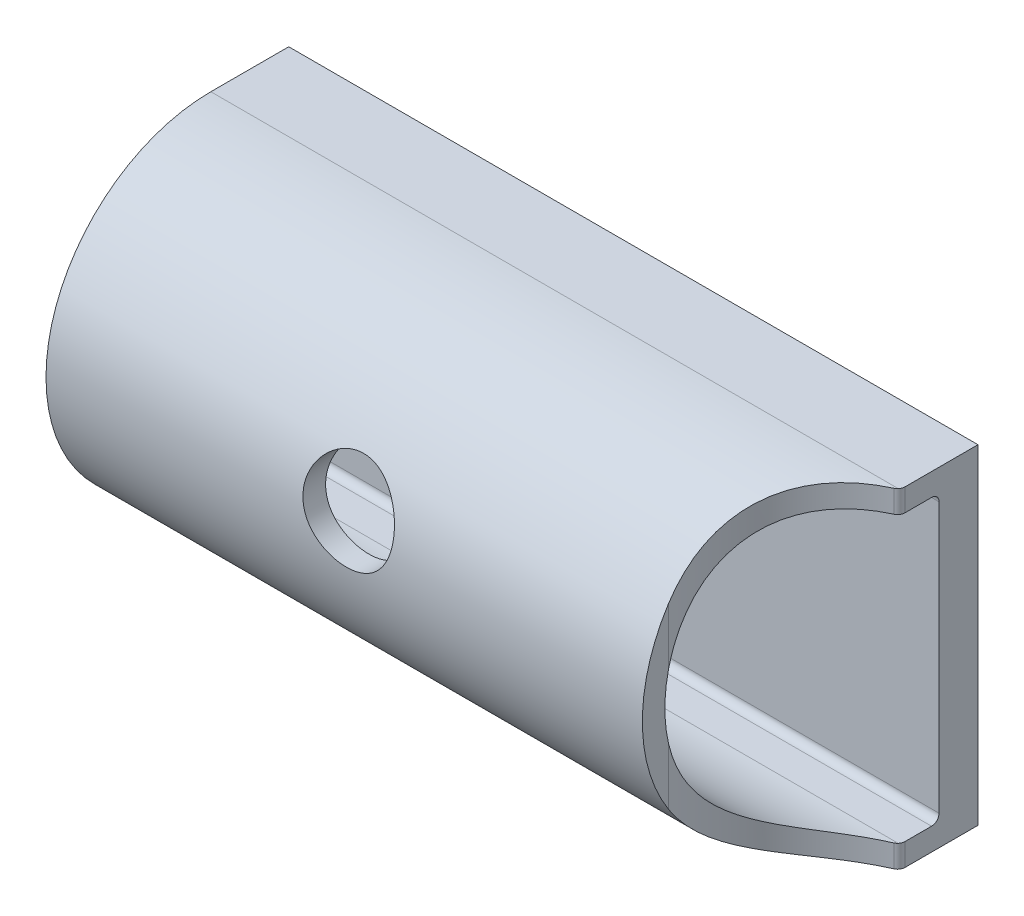
SolidWorks part; units mm, degrees
ref_plane "Front Plane" through (0, 0, 0) normal (0, 0, 1) x (1, 0, 0)
ref_plane "Top Plane" through (0, 0, 0) normal (0, 1, 0) x (1, 0, 0)
ref_plane "Right Plane" through (0, 0, 0) normal (1, 0, 0) x (0, 0, -1)
sketch "Sketch1" plane through (0, 0, 0) normal (0, 0, 1) x (1, 0, 0)
  line L0 (22, 2) -> (-2, 2) construction
  line L1 (-22, -9) -> (22, -9)
  line L2 (-22, -9) -> (-22, 9)
  line L3 (-22, 9) -> (22, 9)
  line L4 (22, -9) -> (22, 9)
  line L5 (-22, -9) -> (22, 9) construction
  line L6 (-22, 9) -> (22, -9) construction
  line L7 (-24, 11) -> (24, 11)
  line L8 (24, -11) -> (24, 11)
  line L9 (-24, -11) -> (24, -11)
  line L10 (-24, -11) -> (-24, 11)
  line L11 (-22, 9) -> (-22, 11)
  line L12 (-22, 11) -> (-22, -11)
  circle A0 centre (-2, 2) radius 1.75
  point P0 (0, 0)
  dimension "D5" = 3.5
  dimension "D1" = 18
  dimension "D2" = 44
  dimension "D3" = 24
  dimension "D4" = 7
  dimension "D6" = 2
extrude "Boss-Extrude1" add sketch "Sketch1" along normal blind 2.6 contours L1 L4 L3 L2 A0 | L1 L12 L9 L8 L7 L11 L3 L4 region at (0.0246, -0.0246, 0) region at (0, -9.5099, 0)
sketch "Sketch2" plane through (0, 0, 2.6) normal (0, 0, 1) x (1, 0, 0)
  line L4 (24, 9.5) -> (-20.5, 9.5)
  line L5 (-20.5, 9.5) -> (-20.5, -9.5)
  line L6 (-20.5, -9.5) -> (24, -9.5)
  line L8 (-22, 11) -> (-22, -11)
  line L9 (-22, -11) -> (24, -11)
  line L10 (24, -11) -> (24, 11)
  line L11 (24, 11) -> (-22, 11)
  line L12 (-22, 11) -> (-22, -11)
  line L13 (-22, -11) -> (24, -11)
  line L14 (24, -11) -> (24, 11)
  line L15 (24, 11) -> (-22, 11)
  line M9 (-22, 11) -> (-22, -11)
  line M10 (-22, -11) -> (24, -11)
  line M11 (24, -11) -> (24, 11)
  line M12 (24, 11) -> (-22, 11)
  dimension "D1" = 0
  dimension "D2" = 1.5
extrude "Boss-Extrude2" add sketch "Sketch2" along normal blind 2.6 contours L6 L5 L4 M11 M12 M9 M10 region at (1.75, 10.0099, 2.6)
sketch "Sketch3" plane through (-22, 0, 0) normal (-1, 0, 0) x (0, 0, 1)
  line L0 (5.2, 11) -> (5.2, -11) construction
  line L1 (5.2, 11) -> (5.2, 9.5)
  line L2 (5.2, -9.5) -> (5.2, -11)
  arc A0 (5.2, 11) -> (5.2, -11) centre (5.2, 0) cw
  arc A1 (5.2, 9.5) -> (5.2, -9.5) centre (5.2, 0) cw
  line M7 (5.2, -11) -> (5.2, 11)
  dimension "D1" = 1.5
extrude "Boss-Extrude3" add sketch "Sketch3" against normal offset from surface (39.8 mm away) 6.2 contours A1 A0 M7 region at (-22, 0, 15.954) up to face at (24, 0, 3.25)
sketch "Sketch4" plane through (0, 0, 0) normal (0, 0, -1) x (-1, 0, 0)
  circle A0 centre (2, 2) radius 1.75
extrude "Cut-Extrude1" cut sketch "Sketch4" against normal through all
sketch "Sketch5" plane through (0, 0, 2.6) normal (0, 0, 1) x (1, 0, 0)
  circle A0 centre (-2, 2) radius 3
  dimension "D1" = 6
extrude "Cut-Extrude2" cut sketch "Sketch5" along normal blind 26.2
fillet "Fillet1" radius 10 2 edges at (17.8, 10.25, 5.2) (17.8, -10.25, 5.2)
fillet "Fillet2" radius 0.5 5 edges at (-20.5, 9.5, 3.9) (-20.5, -9.5, 3.9) (-20.5, 0, 2.6) (1.75, 9.5, 2.6) (1.75, -9.5, 2.6)
fillet "Fillet3" radius 0.5 4 edges at (24, -10.25, 5.2) (24, 10.25, 5.2) (-21, -9.5, 5.2) (-21, 9.5, 5.2)
